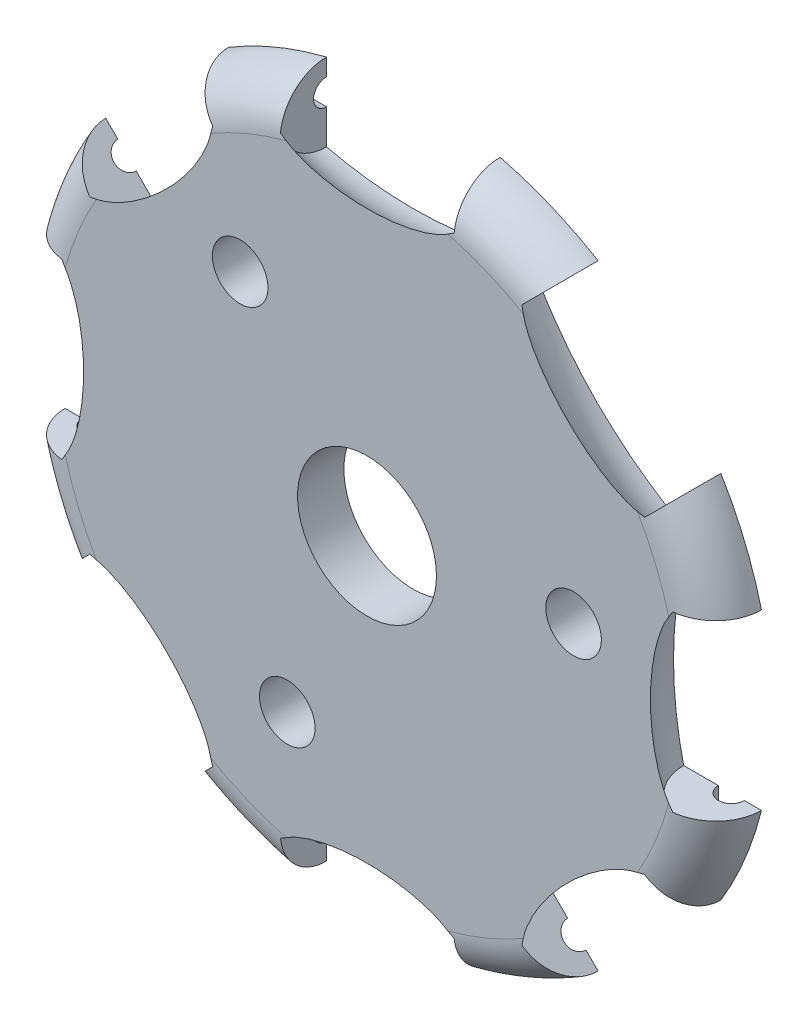
SolidWorks part; units mm, degrees
ref_plane "Front Plane" through (0, 0, 0) normal (0, 0, 1) x (1, 0, 0)
ref_plane "Top Plane" through (0, 0, 0) normal (0, 1, 0) x (1, 0, 0)
ref_plane "Right Plane" through (0, 0, 0) normal (1, 0, 0) x (0, 0, -1)
sketch "Sketch1" plane through (0, 0, 0) normal (0, 0, 1) x (1, 0, 0)
  circle A0 centre (0, 0) radius 24.6062
  dimension "D1" = 49.2125
extrude "Boss-Extrude1" add sketch "Sketch1" along normal blind 3.175
fillet "Fillet1" radius 3.1852 1 edges at (24.6063, 0, 3.175)
sketch "Sketch2" plane through (0, 0, 3.175) normal (0, 0, 1) x (1, 0, 0)
  line L0 (0, 0) -> (-9.4164, -22.7332) construction
  line L1 (0, 0) -> (0, -6.9354) construction
  circle A0 centre (-5.4676, -13.1999) radius 1.905
  circle A1 centre (-8.6977, 11.335) radius 1.905
  circle A2 centre (14.1653, 1.8649) radius 1.905
  circle A3 centre (0, 0) radius 4.7625
  circle A4 centre (0, 0) radius 24.6063 construction
  point P9 (0, 0)
  dimension "D2" = 3.81
  dimension "D4" = 9.525
  dimension "D1" = 14.2875
  dimension "D5" = 22.5
  dimension "D3" = 3
extrude "Cut-Extrude1" cut sketch "Sketch2" against normal through all
sketch "Sketch5" plane through (0, 0, 0) normal (0, 0, 1) x (1, 0, 0)
  line L0 (-5.9531, 21.8122) -> (5.9531, 21.8122)
  line L1 (5.9531, 21.8122) -> (5.9531, 25.0843)
  line L2 (-5.9531, 21.8122) -> (-5.9531, 25.0843)
  line L3 (-5.9531, 21.8122) -> (-8.5086, 21.8122) construction
  arc A0 (-5.9531, 25.0843) -> (5.9531, 25.0843) centre (0, 0) cw
  circle A1 centre (0, 0) radius 24.6063 construction
  point P5 (0, 21.8122)
  point P9 (0, 25.781)
  dimension "D1" = 11.9062
  dimension "D2" = 21.8122
  dimension "D3" = 7.9375
revolve "Cut-Revolve1" cut sketch "Sketch5" angle 360 about L3
sketch "Sketch6" plane through (0, 0, 0) normal (1, 0, 0) x (0, 0, -1)
  line L0 (0, -24.6063) -> (0, 23.8753) construction
  circle A0 centre (0, 21.8122) radius 0.889
  arc A1 (-3.1552, 20.9459) -> (0, 18.5402) centre (0, 21.8122) ccw construction
  dimension "D1" = 1.778
extrude "Cut-Extrude2" cut sketch "Sketch6" against normal mid plane 15.875
pattern_circular "CirPattern1" count 8 over 360 about axis through (0, 0, 0) along (0, 0, 1) of "Cut-Revolve1", "Cut-Extrude2"
